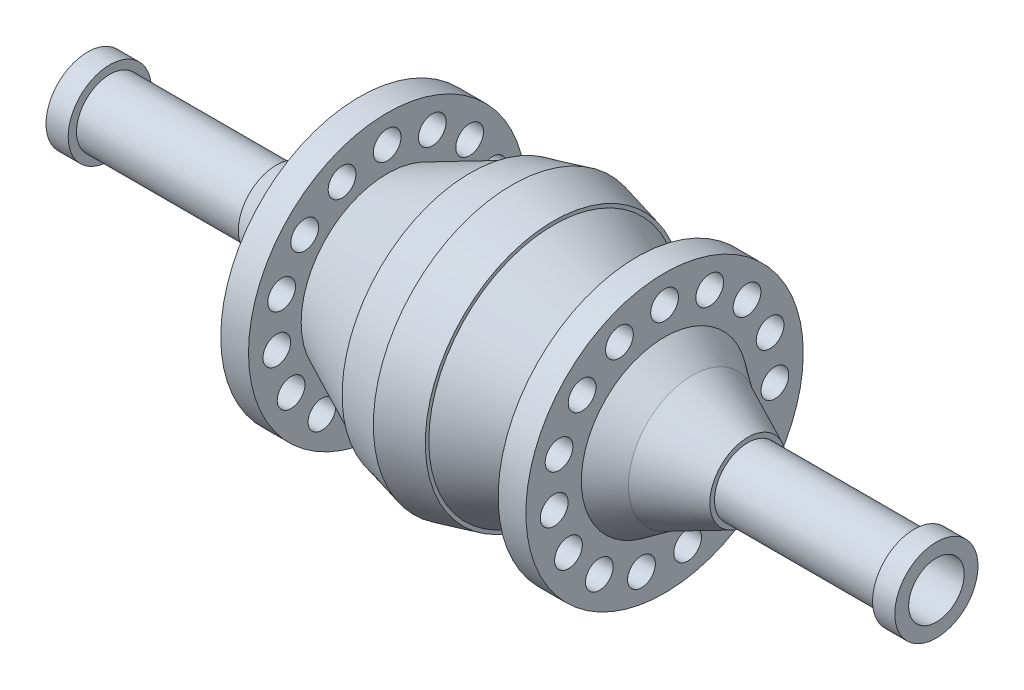
SolidWorks part; units mm, degrees
note: The reader was unsure of these and kept them because the rebuilt part matched: shared geometry of "Sketch6<2>".
ref_plane "Front Plane" through (0, 0, 0) normal (0, 0, 1) x (1, 0, 0)
ref_plane "Top Plane" through (0, 0, 0) normal (0, 1, 0) x (1, 0, 0)
ref_plane "Right Plane" through (0, 0, 0) normal (1, 0, 0) x (0, 0, -1)
sketch "Sketch1" plane through (0, 0, 0) normal (1, 0, 0) x (0, 0, -1)
  circle A0 centre (0, 0) radius 25
  dimension "D1" = 50
extrude "Boss-Extrude1" add sketch "Sketch1" along normal mid plane 15 draft 14 contours A0
sketch "Sketch2" plane through (-7.5, 0, 0) normal (-1, 0, 0) x (0, 0, 1)
  circle A0 centre (0, 0) radius 22.5
  dimension "D1" = 45
extrude "Boss-Extrude2" add sketch "Sketch2" along normal blind 15 draft 25
sketch "Sketch3" plane through (7.5, 0, 0) normal (1, 0, 0) x (0, 0, -1)
  circle A0 centre (0, 0) radius 22.5
  dimension "D1" = 45
extrude "Boss-Extrude3" add sketch "Sketch3" along normal blind 15 draft 25
sketch "Sketch4" plane through (22.5, 0, 0) normal (1, 0, 0) x (0, 0, -1)
  circle A0 centre (0, 0) radius 25
  dimension "D1" = 50
extrude "Boss-Extrude4" add sketch "Sketch4" along normal blind 5
sketch "Sketch5" plane through (-22.5, 0, 0) normal (-1, 0, 0) x (0, 0, 1)
  circle A0 centre (0, 0) radius 25
  dimension "D1" = 50
extrude "Boss-Extrude5" add sketch "Sketch5" along normal blind 5
sketch "Sketch6" plane through (-27.5, 0, 0) normal (-1, 0, 0) x (0, 0, 1)
  circle A0 centre (0, 20) radius 2.5
  circle A1 centre (8.1347, 18.2709) radius 2.5
  circle A2 centre (14.8629, 13.3826) radius 2.5
  circle A3 centre (19.0211, 6.1803) radius 2.5
  circle A4 centre (19.8904, -2.0906) radius 2.5
  circle A20 centre (17.3205, -10) radius 2.5
  circle A21 centre (11.7557, -16.1803) radius 2.5
  circle A22 centre (4.1582, -19.563) radius 2.5
  circle A23 centre (-4.1582, -19.563) radius 2.5
  circle A24 centre (-11.7557, -16.1803) radius 2.5
  circle A25 centre (-17.3205, -10) radius 2.5
  circle A26 centre (-19.8904, -2.0906) radius 2.5
  circle A27 centre (-19.0211, 6.1803) radius 2.5
  circle A28 centre (-14.8629, 13.3826) radius 2.5
  circle A29 centre (-8.1347, 18.2709) radius 2.5
  point P43 (0, 0)
  dimension "D1" = 5
  dimension "D3" = 20
  dimension "D2" = 15
extrude "Cut-Extrude1" cut sketch "Sketch6" against normal up to surface (5 mm away) up to face at (-22.5, 0, 15.5054)
extrude "Cut-Extrude2" cut sketch "Sketch6<2>" against normal blind 5 from offset 50 offset against normal yes
sketch "Sketch6<2>" plane through (-27.5, 0, 0) normal (-1, 0, 0) x (0, 0, 1) same geometry as "Sketch6"
sketch "Sketch7" plane through (-27.5, 0, 0) normal (-1, 0, 0) x (0, 0, 1)
  circle A0 centre (0, 0) radius 15
  dimension "D1" = 30
extrude "Boss-Extrude6" add sketch "Sketch7" along normal blind 5 draft 35
sketch "Sketch8" plane through (-32.5, 0, 0) normal (-1, 0, 0) x (0, 0, 1)
  circle A0 centre (0, 0) radius 11.499
  circle A1 centre (0, 0) radius 11.499 construction
extrude "Boss-Extrude7" add sketch "Sketch8" along normal blind 10 draft 25
sketch "Sketch10" plane through (-42.5, 0, 0) normal (-1, 0, 0) x (0, 0, 1)
  circle A0 centre (0, 0) radius 6
  dimension "D1" = 12
extrude "Boss-Extrude8" add sketch "Sketch10" along normal blind 30
sketch "Sketch11" plane through (-72.5, 0, 0) normal (-1, 0, 0) x (0, 0, 1)
  circle A1 centre (0, 0) radius 7.5
  dimension "D1" = 15
extrude "Boss-Extrude10" add sketch "Sketch11" along normal blind 4 contours A1
sketch "Sketch14" plane through (27.5, 0, 0) normal (1, 0, 0) x (0, 0, -1)
  circle A0 centre (0, 0) radius 15
  dimension "D1" = 30
extrude "Boss-Extrude11" add sketch "Sketch14" along normal blind 5 draft 35
sketch "Sketch16" plane through (32.5, 0, 0) normal (1, 0, 0) x (0, 0, -1)
  circle A0 centre (0, 0) radius 11.5093
extrude "Boss-Extrude12" add sketch "Sketch16" along normal blind 10 draft 25
sketch "Sketch17" plane through (42.5, 0, 0) normal (1, 0, 0) x (0, 0, -1)
  circle A0 centre (0, 0) radius 6
  dimension "D1" = 12
extrude "Boss-Extrude13" add sketch "Sketch17" along normal blind 30 contours A0
sketch "Sketch18" plane through (72.5, 0, 0) normal (1, 0, 0) x (0, 0, -1)
  circle A0 centre (0, 0) radius 7.5
  dimension "D1" = 15
extrude "Boss-Extrude14" add sketch "Sketch18" along normal blind 4
sketch "Sketch20" plane through (-76.5, 0, 0) normal (-1, 0, 0) x (0, 0, 1)
  circle A0 centre (0, 0) radius 5
extrude "Cut-Extrude3" cut sketch "Sketch20" against normal up to surface (119 mm away)
mirror "Mirror1" about plane through (0, 0, 0) normal (1, 0, 0) of "Cut-Extrude3"
